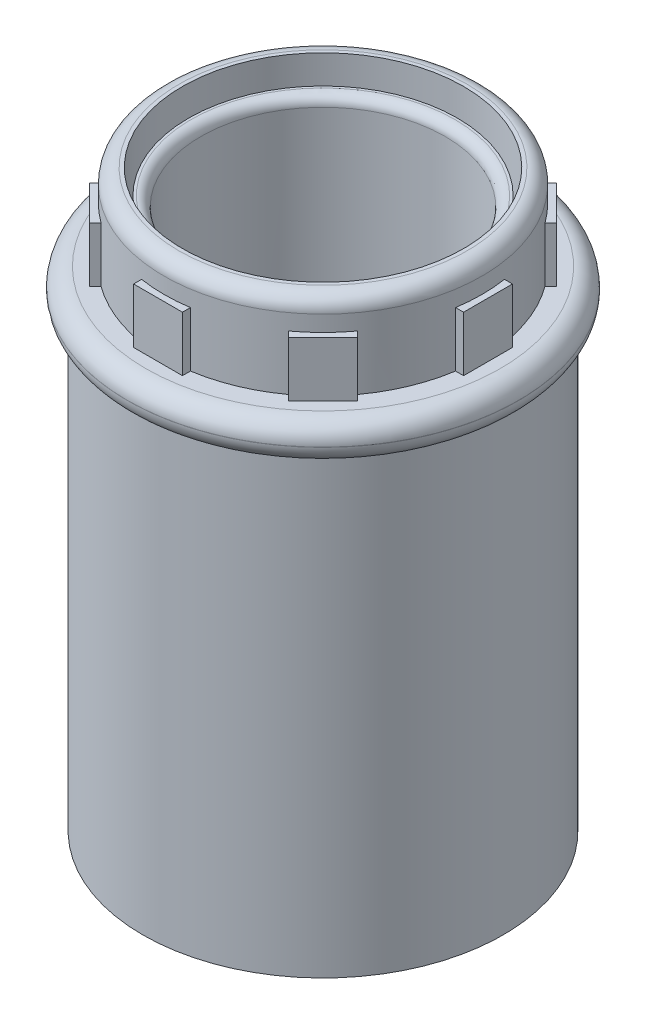
SolidWorks part; units mm, degrees
material "Natural Rubber"
ref_plane "Front Plane" through (0, 0, 0) normal (0, 0, 1) x (1, 0, 0)
ref_plane "Top Plane" through (0, 0, 0) normal (0, 1, 0) x (1, 0, 0)
ref_plane "Right Plane" through (0, 0, 0) normal (1, 0, 0) x (0, 0, -1)
sketch "Sketch1" plane through (0, 0, 0) normal (0, 1, 0) x (1, 0, 0)
  circle A0 centre (0, 0) radius 14.75
  dimension "D1" = 29.5
extrude "Boss-Extrude1" add sketch "Sketch1" along normal blind 37
sketch "Sketch2" plane through (0, 37, 0) normal (0, 1, 0) x (1, 0, 0)
  circle A0 centre (0, 0) radius 16
  dimension "D1" = 32
extrude "Boss-Extrude2" add sketch "Sketch2" along normal blind 3
fillet "Fillet1" radius 1.5 2 edges at (0, 40, 16) (0, 37, 16)
sketch "Sketch3" plane through (0, 40, 0) normal (0, 1, 0) x (1, 0, 0)
  circle A0 centre (0, 0) radius 10
extrude "Cut-Extrude1" cut sketch "Sketch3" against normal blind 20
sketch "Sketch5" plane through (0, 20, 0) normal (0, 1, 0) x (1, 0, 0)
  line L0 (0, -17.6) -> (0, 17.6) construction
  line L1 (-9, 2) -> (-9, -2)
  line L2 (-9, 2) -> (-5.6569, 2)
  line L3 (-9, -2) -> (-5.6569, -2)
  line L4 (9, -2) -> (5.6569, -2)
  line L5 (9, 2) -> (9, -2)
  line L6 (9, 2) -> (5.6569, 2)
  arc A0 (-5.6569, -2) -> (5.6569, -2) centre (0, 0) ccw
  arc A1 (5.6569, 2) -> (-5.6569, 2) centre (0, 0) ccw
  point P8 (-9, 0)
extrude "Cut-Extrude2" cut sketch "Sketch5" against normal blind 30
cosmetic thread "Cosmetic Thread1" parameters "D1"=15, "D2"=13
cosmetic thread "Cosmetic Thread2" parameters "D1"=15, "D2"=13
sketch "Sketch6" plane through (0, 0, 0) normal (0, 0, 1) x (1, 0, 0)
  line L0 (-10, 40) -> (10, 40)
  line L2 (-10, 40) -> (-10, 44.2)
  line L3 (10, 40) -> (10, 44.2)
  line L4 (-10.8, 45) -> (-11, 45)
  line L5 (-11, 45) -> (-11, 40)
  line L6 (14.5, 40) -> (-14.5, 40) construction
  line L7 (10.8, 45) -> (11, 45)
  line L8 (11, 45) -> (11, 40)
  line L9 (-11, 40) -> (-11.5, 40)
  line L10 (-11.5, 40) -> (-11.5, 47)
  line L11 (-11.5, 47) -> (-11.8, 47)
  line L12 (-13, 45.8) -> (-13, 40)
  line L13 (0, -17.6) -> (0, 17.6) construction
  line L14 (11.5, 40) -> (11.5, 47)
  line L15 (11.5, 47) -> (11.8, 47)
  line L16 (13, 45.8) -> (13, 40)
  line L17 (-13, 40) -> (-11.5, 40)
  line L18 (-10, 40) -> (-11, 40)
  line L19 (10, 40) -> (11, 40)
  line L20 (11.5, 40) -> (13, 40)
  line L21 (0, 40) -> (0, 54.174) construction
  arc A0 (10, 44.2) -> (10.8, 45) centre (10.8, 44.2) cw
  arc A1 (-10, 44.2) -> (-10.8, 45) centre (-10.8, 44.2) ccw
  arc A2 (11.8, 47) -> (13, 45.8) centre (11.8, 45.8) cw
  arc A3 (-11.8, 47) -> (-13, 45.8) centre (-11.8, 45.8) ccw
  point P3 (0, 40)
  point P28 (13, 47)
  point P31 (-13, 47)
  dimension "D1" = 0.8
  dimension "D2" = 1.2
revolve "Revolve1" add sketch "Sketch6" angle 360 about L21 region at (-10.5091, 42.4344, 0) region at (-12.2354, 43.402, 0)
ref_plane "Plane1" through (0, 0, 13) normal (0, 0, 1) x (1, 0, 0)
sketch "Sketch7" plane through (0, 0, 13) normal (0, 0, 1) x (1, 0, 0)
  line L3 (-2, 40) -> (2, 40)
  line L4 (-2, 40) -> (-2, 44.5)
  line L5 (-2, 44.5) -> (2, 44.5)
  line L6 (2, 44.5) -> (2, 40)
  point P8 (0, 40)
extrude "Boss-Extrude3" add sketch "Sketch7" along normal blind 0.5 and the other way up to surface other way up to face at (0, 40, -13)
pattern_circular "CirPattern1" count 8 every 45 about axis through (0, 40, 0) along (0, -1, 0) of "Boss-Extrude3"
fillet "Fillet2" radius 1 8 edges at (7.3284, 20, 2) (7.3284, 20, -2) (9, 20, 0) (0, 20, -6) (-9, 20, 0) (-7.3284, 20, -2) (-7.3284, 20, 2) (0, 20, 6)
